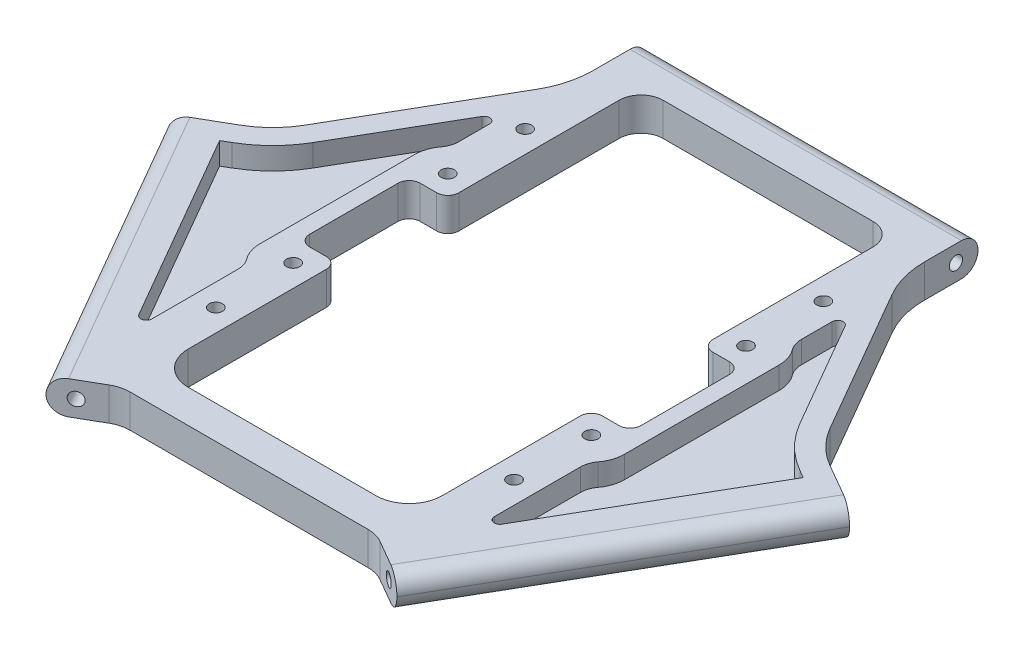
SolidWorks part; units mm, degrees
ref_plane "前视基准面" through (0, 0, 0) normal (0, 0, 1) x (1, 0, 0)
ref_plane "上视基准面" through (0, 0, 0) normal (0, 1, 0) x (1, 0, 0)
ref_plane "右视基准面" through (0, 0, 0) normal (1, 0, 0) x (0, 0, -1)
sketch "Sketch1" plane through (0, 0, 0) normal (0, 1, 0) x (1, 0, 0)
  line L0 (0, 92) -> (-79.6743, -46) construction
  line L1 (-79.6743, -46) -> (79.6743, -46) construction
  line L2 (0, 92) -> (79.6743, -46) construction
  line L3 (0, 0) -> (0, 92) construction
  line L4 (0, 0) -> (39.8372, 23) construction
  line L5 (-30, 54) -> (30, 54)
  line L6 (61.7654, -1.0192) -> (31.7654, -52.9808)
  line L7 (-31.7654, -52.9808) -> (-61.7654, -1.0192)
  line L8 (-30, 54) -> (-30, 40.0385)
  line L9 (-30, 40.0385) -> (-49.6743, 5.9615)
  line L10 (-49.6743, 5.9615) -> (-61.7654, -1.0192)
  line L11 (61.7654, -1.0192) -> (49.6743, 5.9615)
  line L12 (49.6743, 5.9615) -> (30, 40.0385)
  line L13 (30, 40.0385) -> (30, 54)
  line L14 (-31.7654, -52.9808) -> (-19.6743, -46) construction
  line L15 (-15, 50) -> (15, 50) construction
  line L16 (19.6743, -46) -> (31.7654, -52.9808) construction
  line L17 (50.8013, -12.0096) -> (35.8013, -37.9904) construction
  line L18 (-35.8013, -37.9904) -> (-50.8013, -12.0096) construction
  line L19 (-21, -46.7654) -> (-21, 18) construction
  line L20 (-21, 18) -> (21, 18) construction
  line L21 (21, -46.7654) -> (21, 18) construction
  line L22 (-19.6743, -46) -> (19.6743, -46) construction
  line L23 (-19.6743, -46) -> (19.6743, -46) [skipped]
  line L24 (-31.7654, -52.9808) -> (-23.1384, -48)
  line L25 (-23.1384, -48) -> (23.1384, -48)
  line L26 (23.1384, -48) -> (31.7654, -52.9808)
  circle A0 centre (15, 50) radius 1.45 construction
  circle A1 centre (-15, 50) radius 1.45 construction
  circle A2 centre (50.8013, -12.0096) radius 1.45 construction
  circle A3 centre (35.8013, -37.9904) radius 1.45 construction
  circle A4 centre (-35.8013, -37.9904) radius 1.45 construction
  circle A5 centre (-50.8013, -12.0096) radius 1.45 construction
  point P8 (0, 54)
  point P16 (0, 0)
  point P22 (0, 18)
  point P25 (0, 50)
  point P27 (0, 0)
  point P42 (0, 0)
  dimension "D5" = 3
  dimension "D4" = 3
  dimension "D10" = 2.9
  dimension "D1" = 46
  dimension "D3" = 60
  dimension "D6" = 42
  dimension "D7" = 18
  dimension "D8" = 50
  dimension "D9" = 30
  dimension "D2" = 4
  dimension "D12" = 18.8135
  dimension "D13" = 2
  dimension "D11" = 3
extrude "Boss-Extrude1" add sketch "Sketch1" along normal blind 6
sketch "Sketch2" plane through (-30, 0, 0) normal (-1, 0, 0) x (0, 0, 1)
  line L0 (-53, -1) -> (-47, -1) construction
  line L2 (-45, 3) -> (-45, 6) construction
  line L3 (-54, 6) -> (-40.0385, 6) construction
  line L4 (-45, 6) -> (-55, 6) construction
  line L5 (-55, 3) -> (-55, 6) construction
  line L6 (-54, 0) -> (-40.0385, 0) construction
  arc A0 (-47, -1) -> (-45, 3) centre (-50, 3) ccw construction
  arc A1 (-55, 3) -> (-53, -1) centre (-50, 3) ccw construction
  circle A2 centre (-50, 3) radius 1.2
  dimension "D2" = 10
  dimension "D6" = 2.4
  dimension "D1" = 50
  dimension "D3" = 4
  dimension "D5" = 3
  dimension "D4" = 3
sketch "Sketch4" plane through (-15, 0, -25.9808) normal (-0.5, 0, -0.866) x (-0.866, 0, 0.5)
  line L0 (53, -1) -> (47, -1) construction
  line L2 (40.0385, 0) -> (54, 0) construction
  line L3 (45, 3) -> (45, 6) construction
  line L4 (40.0385, 6) -> (54, 6) construction
  line L5 (45, 6) -> (55, 6) construction
  line L6 (55, 6) -> (55, 3) construction
  arc A0 (45, 3) -> (47, -1) centre (50, 3) ccw construction
  arc A1 (53, -1) -> (55, 3) centre (50, 3) ccw construction
  circle A2 centre (50, 3) radius 1.2
  dimension "D1" = 10
  dimension "D5" = 2.4
  dimension "D3" = 50
  dimension "D4" = 4
  dimension "D2" = 3
sketch "Sketch6" plane through (15, 0, -25.9808) normal (0.5, 0, -0.866) x (-0.866, 0, -0.5)
  line L0 (-47, -1) -> (-53, -1) construction
  line L2 (-55, 3) -> (-55, 6) construction
  line L3 (-54, 6) -> (-40.0385, 6) construction
  line L4 (-55, 6) -> (-45, 6) construction
  line L5 (-45, 6) -> (-45, 3) construction
  line L6 (-54, 0) -> (-40.0385, 0) construction
  arc A0 (-47, -1) -> (-45, 3) centre (-50, 3) ccw construction
  arc A1 (-55, 3) -> (-53, -1) centre (-50, 3) ccw construction
  circle A2 centre (-50, 3) radius 1.2
  dimension "D5" = 2.4
  dimension "D3" = 50
  dimension "D2" = 3
  dimension "D4" = 5
  dimension "D1" = 4
extrude "Cut-Extrude1" cut sketch "Sketch6" against normal blind 104 contours A2
cosmetic thread "Cosmetic Thread3" parameters "D2"=3
cosmetic thread "Cosmetic Thread4" parameters "D2"=3
extrude "Cut-Extrude2" cut sketch "Sketch4" against normal blind 104
cosmetic thread "Cosmetic Thread5" parameters "D2"=3
cosmetic thread "Cosmetic Thread6" parameters "D2"=3
extrude "Cut-Extrude3" cut sketch "Sketch2" against normal blind 104
cosmetic thread "Cosmetic Thread1" parameters "D2"=3
cosmetic thread "Cosmetic Thread2" parameters "D2"=3
fillet "Fillet2" radius 3 6 edges at (46.7654, 0, 27) (46.7654, 6, 27) (-46.7654, 6, 27) (-46.7654, 0, 27) (0, 0, -54) (0, 6, -54)
ref_plane "Plane1" through (-16, 0, 0) normal (-1, 0, 0) x (0, 0, 1)
sketch "Sketch11" plane through (-16, 0, 0) normal (-1, 0, 0) x (0, 0, 1)
  circle A0 centre (-50, 3) radius 1.2 construction
  circle A1 centre (-50, 3) radius 1.2
extrude "Boss-Extrude3" add sketch "Sketch11" against normal offset from surface (32 mm away) 14 up to face at (30, 3, -48.8)
ref_plane "Plane2" through (8, 0, -13.8564) normal (0.5, 0, -0.866) x (-0.866, 0, -0.5)
sketch "Sketch13" plane through (8, 0, -13.8564) normal (0.5, 0, -0.866) x (-0.866, 0, -0.5)
  circle A0 centre (-50, 3) radius 1.2 construction
  circle A1 centre (-50, 3) radius 1.2
extrude "Boss-Extrude4" add sketch "Sketch13" against normal offset from surface (32 mm away) 14 up to face at (27.262, 3, 50.3808)
ref_plane "Plane3" through (8, 0, 13.8564) normal (0.5, 0, 0.866) x (0.866, 0, -0.5)
sketch "Sketch14" plane through (8, 0, 13.8564) normal (0.5, 0, 0.866) x (0.866, 0, -0.5)
  circle A1 centre (-50, 3) radius 1.2
  circle A2 centre (-50, 3) radius 1.2 construction
extrude "Boss-Extrude5" add sketch "Sketch14" against normal offset from surface (32 mm away) 14 up to face at (-59.3405, 3, -0.3808)
sketch "Sketch16" plane through (0, 6, 0) normal (0, 1, 0) x (1, 0, 0)
  line L0 (0, 0) -> (0, -42) construction
  line L1 (-23, 46) -> (23, 46)
  line L2 (-23, 46) -> (-23, -42)
  line L3 (-23, -42) -> (23, -42)
  line L4 (23, 46) -> (23, -42)
  line L5 (-23.1384, -48) -> (23.1384, -48) construction
  line L6 (-30, 54) -> (30, 54) construction
  dimension "D1" = 46
  dimension "D2" = 8
  dimension "D3" = 6
extrude "Cut-Extrude5" cut sketch "Sketch16" against normal blind 10
sketch "Sketch15" plane through (0, 6, 0) normal (0, 1, 0) x (1, 0, 0)
  line L0 (0, 0) -> (0, 15) construction
  line L1 (-27, 29) -> (-27, 15) construction
  line L4 (27, 29) -> (27, 15) construction
  circle A0 centre (27, 29) radius 1.2
  circle A1 centre (-27, 15) radius 1.2
  circle A2 centre (-27, 29) radius 1.2
  circle A3 centre (27, 15) radius 1.2
  dimension "D4" = 2.4
  dimension "D1" = 27
  dimension "D2" = 15
  dimension "D3" = 14
extrude "Cut-Extrude4" cut sketch "Sketch15" against normal blind 10
cosmetic thread "Cosmetic Thread7" parameters "D2"=3
cosmetic thread "Cosmetic Thread8" parameters "D2"=3
fillet "Fillet3" radius 6 2 edges at (23, 3, 42) (-23, 3, 42)
fillet "Fillet1" radius 16 4 edges at (-30, 3, -40.0385) (-49.6743, 3, -5.9615) (30, 3, -40.0385) (49.6743, 3, -5.9615)
fillet "Fillet4" radius 6 2 edges at (23.1384, 3, 48) (-23.1384, 3, 48)
fillet "Fillet5" radius 4 2 edges at (23, 3, -46) (-23, 3, -46)
sketch "Sketch17" plane through (0, 6, 0) normal (0, 1, 0) x (1, 0, 0)
  line L0 (23, -36) -> (23, 42) construction
  line L1 (23, 11) -> (28, 11)
  line L2 (23, 11) -> (23, -9)
  line L3 (23, -9) -> (28, -9)
  line L4 (30, 9) -> (30, -7)
  line L5 (0, 54) -> (0, 0) construction
  line L6 (-30, 54) -> (30, 54) construction
  line L7 (-30, 9) -> (-30, -7)
  line L8 (-23, -9) -> (-28, -9)
  line L9 (-23, 11) -> (-23, -9)
  line L10 (-23, 11) -> (-28, 11)
  line L11 (19, 46) -> (-19, 46) construction
  line L12 (-17, -42) -> (17, -42) construction
  circle A0 centre (27, 15) radius 1.2 construction
  arc A1 (-30, -7) -> (-28, -9) centre (-28, -7) ccw
  arc A2 (-30, 9) -> (-28, 11) centre (-28, 9) cw
  arc A3 (28, -9) -> (30, -7) centre (28, -7) ccw
  arc A4 (28, 11) -> (30, 9) centre (28, 9) cw
  point P19 (-30, -9)
  point P22 (-30, 11)
  point P25 (30, -9)
  point P28 (30, 11)
  dimension "D4" = 2
  dimension "D1" = 4
  dimension "D2" = 7
  dimension "D3" = 20
  dimension "D5" = 35
  dimension "D6" = 33
extrude "Cut-Extrude6" cut sketch "Sketch17" against normal blind 10
fillet "Fillet6" radius 2 4 edges at (23, 3, -11) (23, 3, 9) (-23, 3, 9) (-23, 3, -11)
sketch "Sketch18" plane through (0, 6, 0) normal (0, 1, 0) x (1, 0, 0)
  line L0 (-30, 1) -> (30, 1) construction
  line L1 (-30, 9) -> (-30, -7) construction
  line L2 (30, -7) -> (30, 9) construction
  line L3 (-27, 29) -> (-27, 15) construction
  line L4 (-27, 15) -> (27, 15) construction
  line L5 (27, 15) -> (27, 29) construction
  line L6 (27, 29) -> (-27, 29) construction
  line L7 (27, -27) -> (-27, -27) construction
  line L8 (27, -13) -> (27, -27) construction
  line L9 (-27, -13) -> (27, -13) construction
  line L10 (-27, -27) -> (-27, -13) construction
  circle A0 centre (27, -13) radius 1.2
  circle A1 centre (27, -27) radius 1.2
  circle A2 centre (-27, -13) radius 1.2
  circle A3 centre (-27, -27) radius 1.2
  circle A4 centre (27, 15) radius 1.2 construction
  circle A6 centre (-27, 15) radius 1.2 construction
extrude "Cut-Extrude7" cut sketch "Sketch18" against normal blind 10
cosmetic thread "Cosmetic Thread11" parameters "D2"=3
cosmetic thread "Cosmetic Thread12" parameters "D2"=3
cosmetic thread "Cosmetic Thread13" parameters "D2"=3
cosmetic thread "Cosmetic Thread14" parameters "D2"=3
sketch "Sketch19" plane through (0, 6, 0) normal (0, 1, 0) x (1, 0, 0)
  line L0 (31, 26.5744) -> (31, 21)
  line L1 (33, 15) -> (33, -13)
  line L2 (32.866, 27.0744) -> (44.0666, 7.6743)
  line L3 (47.5307, 9.6743) -> (32.1436, 36.3257) construction
  line L4 (31, -19) -> (31, -34.5744)
  line L5 (51.3872, 0.3538) -> (52.8372, -0.4833)
  line L6 (52.8372, -0.4833) -> (32.866, -35.0744)
  line L7 (61.7654, -1.0192) -> (31.7654, -52.9808) construction
  line L8 (0, 46) -> (0, -42) construction
  line L9 (19, 46) -> (-19, 46) construction
  line L10 (-17, -42) -> (17, -42) construction
  line L11 (-52.8372, -0.4833) -> (-32.866, -35.0744)
  line L12 (-51.3872, 0.3538) -> (-52.8372, -0.4833)
  line L13 (-31, -19) -> (-31, -34.5744)
  line L14 (-32.866, 27.0744) -> (-44.0666, 7.6743)
  line L15 (-33, 15) -> (-33, -13)
  line L16 (-31, 26.5744) -> (-31, 21)
  arc A0 (33, 15) -> (31.8, 18.6) centre (27, 15) ccw
  arc A1 (31.8, -16.6) -> (33, -13) centre (27, -13) ccw
  circle A2 centre (27, 15) radius 1.2 construction
  arc A3 (31, -34.5744) -> (32.866, -35.0744) centre (32, -34.5744) ccw
  arc A4 (31, 26.5744) -> (32.866, 27.0744) centre (32, 26.5744) cw
  arc A5 (44.0666, 7.6743) -> (51.3872, 0.3538) centre (61.3872, 17.6743) ccw
  arc A6 (44.0666, 7.6743) -> (51.3872, 0.3538) centre (61.3872, 17.6743) ccw
  arc A7 (31, -19) -> (31.8, -16.6) centre (35, -19) cw
  arc A8 (31.8, 18.6) -> (31, 21) centre (35, 21) cw
  arc A9 (-31.8, 18.6) -> (-31, 21) centre (-35, 21) ccw
  arc A10 (-31, -19) -> (-31.8, -16.6) centre (-35, -19) ccw
  arc A11 (-44.0666, 7.6743) -> (-51.3872, 0.3538) centre (-61.3872, 17.6743) cw
  arc A12 (-31, 26.5744) -> (-32.866, 27.0744) centre (-32, 26.5744) ccw
  arc A13 (-31, -34.5744) -> (-32.866, -35.0744) centre (-32, -34.5744) cw
  arc A14 (-31.8, -16.6) -> (-33, -13) centre (-27, -13) cw
  arc A15 (-33, 15) -> (-31.8, 18.6) centre (-27, 15) cw
  dimension "D1" = 12
  dimension "D5" = 1
  dimension "D6" = 4
  dimension "D2" = 4
  dimension "D3" = 8
  dimension "D4" = 4
extrude "Cut-Extrude8" cut sketch "Sketch19" against normal blind 4
equation "\"D1@Sketch2\" = \"D8@Sketch1\""
equation "\"D3@Sketch4\" = \"D8@Sketch1\""
equation "\"D3@Sketch6\" = \"D8@Sketch1\""
